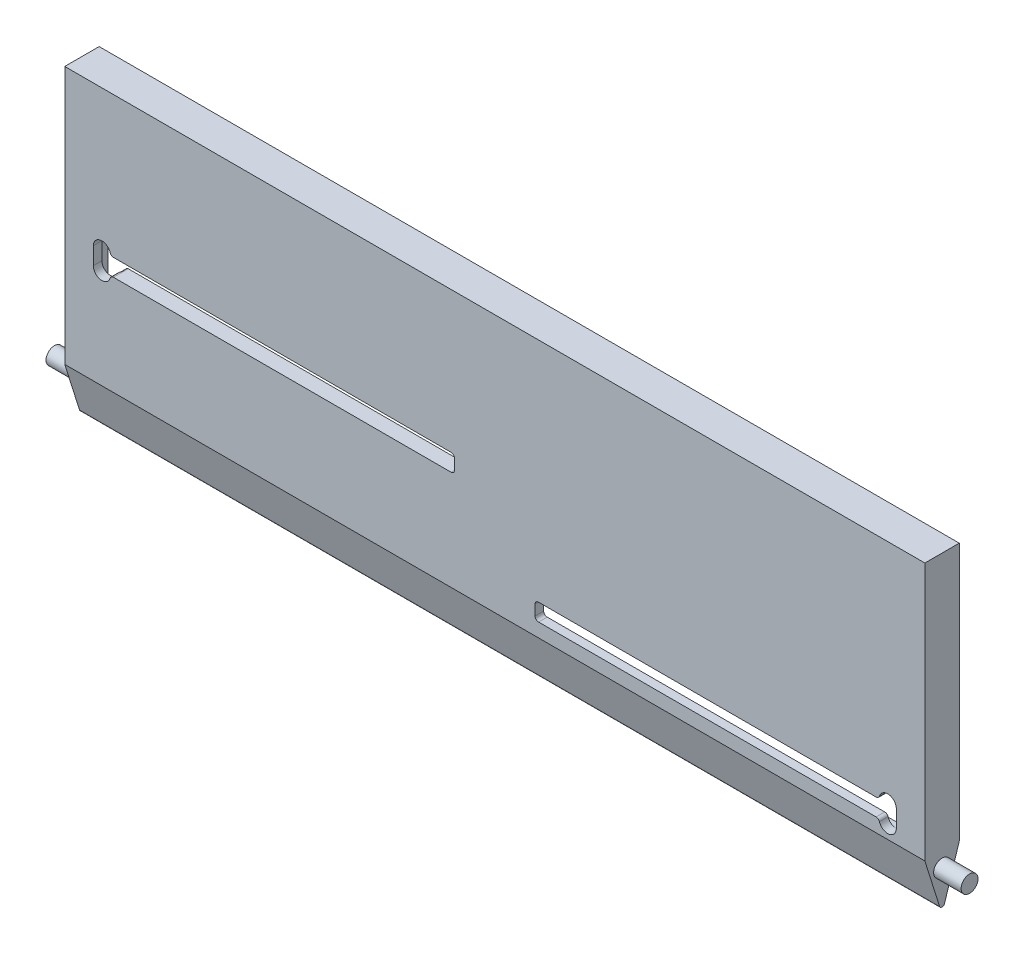
SolidWorks part; units mm, degrees
material "ABS"
ref_plane "Face" through (0, 0, 0) normal (0, 0, 1) x (1, 0, 0)
ref_plane "Dessus" through (0, 0, 0) normal (0, 1, 0) x (1, 0, 0)
ref_plane "Droite" through (0, 0, 0) normal (1, 0, 0) x (0, 0, -1)
sketch "Esquisse1" plane through (0, 0, 0) normal (1, 0, 0) x (0, 0, -1)
  line L0 (5, 15.858) -> (0, 0)
  line L1 (-5, 15.858) -> (5, 15.858) construction
  line L2 (-5, 15.858) -> (-5, 90.858)
  line L3 (-5, 90.858) -> (5, 90.858)
  line L4 (5, 15.858) -> (5, 90.858)
  line L5 (0, 0) -> (-5, 15.858)
  line L6 (0, 15.858) -> (0, 0) construction
  dimension "D1" = 10
  dimension "D2" = 75
  dimension "D3" = 35
extrude "Boss.-Extru.1" add sketch "Esquisse1" along normal blind 125
sketch "Esquisse2" plane through (125, 0, 0) normal (-1, 0, 0) x (0, 0, 1)
  line L2 (-2.3843, 10.8875) -> (0, 3.3255) construction
  line L3 (0, 3.3255) -> (2.3843, 10.8875) construction
  line L4 (5, 15.858) -> (0, 0) construction
  line L5 (0, 0) -> (-5, 15.858) construction
  circle A0 centre (0, 11.6393) radius 2.5 construction
  circle A1 centre (0, 11.6393) radius 2.45
  dimension "D1" = 5
  dimension "D4" = 4.9
  dimension "D2" = 1
  dimension "D3" = 1
extrude "Boss.-Extru.2" add sketch "Esquisse2" against normal blind 8
mirror "Symétrie1" about plane through (0, 0, 0) normal (1, 0, 0) of "Boss.-Extru.1", "Boss.-Extru.2"
fillet "Congé1" radius 0.75 1 edges at (0, 0, 0)
shell "Coque1" thickness 2.5 removed face at (0, 9.0633, -2.8576) removed face at (0, 53.358, -5)
sketch "Esquisse3" plane through (0, 0, 5) normal (0, 0, 1) x (1, 0, 0)
  line L0 (114.2, 19.858) -> (114.2, 24.858) construction
  line L2 (116.7, 19.858) -> (116.7, 24.858)
  line L3 (114.2, 22.358) -> (116.7, 22.358) construction
  line L4 (110.8459, 24.858) -> (12.7, 24.858)
  line L6 (110.8459, 19.858) -> (12.7, 19.858)
  line L7 (11.7, 23.858) -> (11.7, 20.858)
  line L8 (125, 90.858) -> (125, 15.858) construction
  line L9 (125, 15.858) -> (-125, 15.858) construction
  arc A0 (111.8042, 19.1437) -> (116.7, 19.858) centre (114.2, 19.858) ccw
  arc A1 (116.7, 24.858) -> (111.8042, 25.5723) centre (114.2, 24.858) ccw
  arc A2 (12.7, 24.858) -> (11.7, 23.858) centre (12.7, 23.858) ccw
  arc A3 (12.7, 19.858) -> (11.7, 20.858) centre (12.7, 20.858) cw
  arc A4 (110.8459, 24.858) -> (111.8042, 25.5723) centre (110.8459, 25.858) ccw
  arc A5 (110.8459, 19.858) -> (111.8042, 19.1437) centre (110.8459, 18.858) cw
  point P11 (114.2, 22.358)
  point P34 (11.7, 24.858)
  point P39 (111.7, 24.858)
  dimension "D1" = 10
  dimension "D6" = 1
  dimension "D7" = 1
  dimension "D2" = 8.3
  dimension "D3" = 5
  dimension "D4" = 100
  dimension "D5" = 4
extrude "Enlèv. mat.-Extru.1" cut sketch "Esquisse3" against normal through all
sketch "Esquisse4" plane through (0, 0, 2.5) normal (0, 0, -1) x (-1, 0, 0)
  line L0 (0, 34.858) -> (0, 0) construction
  line L1 (-12.7, 24.858) -> (-110.8459, 24.858) construction
  circle A0 centre (0, 34.858) radius 3.25
  circle A1 centre (0, 34.858) radius 1.65
  dimension "D1" = 6.5
  dimension "D3" = 3.3
  dimension "D2" = 10
extrude "Boss.-Extru.3" add sketch "Esquisse4" along normal blind 6
ref_axis "Axe1" through (0, 34.858, -3.5) along (0, 0, 1)
pattern_circular "Répétition circulaire1" count 2 over 360 about axis through (0, 34.858, -3.5) along (0, 0, 1) of "Enlèv. mat.-Extru.1"
sketch "Esquisse5" plane through (0, 0, 2.5) normal (0, 0, -1) x (-1, 0, 0)
  line L0 (-13.25, 39.858) -> (-13.25, 29.858) construction
  line L1 (13.25, 39.858) -> (13.25, 29.858) construction
  line L2 (-13.25, 34.858) -> (13.25, 34.858) construction
  line L10 (-12.7, 25.558) -> (-110.8459, 25.558)
  line L11 (-12.7, 25.558) -> (-110.8459, 25.558) construction
  line L12 (-12.7, 25.558) -> (122.5, 25.558) construction
  line L13 (12.7, 44.158) -> (110.8459, 44.158)
  line L14 (12.7, 44.158) -> (110.8459, 44.158) construction
  line L15 (122.5, 15.858) -> (122.5, 88.358) construction
  line L16 (12.7, 44.158) -> (-122.5, 44.158) construction
  line L17 (-122.5, 88.358) -> (-122.5, 16.2428) construction
  line L18 (-122.5, 16.558) -> (122.5, 16.558) construction
  line L20 (122.5, 88.358) -> (122.5, 16.2428) construction
  line L21 (-122.5, 53.158) -> (122.5, 53.158) construction
  line L22 (-13.95, 39.858) -> (-13.95, 29.858)
  line L23 (12.55, 39.858) -> (12.55, 29.858)
  line L24 (-12.7, 26.258) -> (122.5, 26.258)
  line L25 (-12.7, 26.258) -> (-110.8459, 26.258)
  line L26 (-122.5, 15.858) -> (122.5, 15.858)
  line L27 (12.7, 43.458) -> (-122.5, 43.458)
  line L28 (12.7, 43.458) -> (110.8459, 43.458)
  line L29 (-122.5, 52.458) -> (122.5, 52.458)
  line L30 (-12.55, 39.858) -> (-12.55, 29.858)
  line L31 (13.95, 39.858) -> (13.95, 29.858)
  line L32 (-12.7, 24.858) -> (122.5, 24.858)
  line L33 (-12.7, 24.858) -> (-110.8459, 24.858)
  line L34 (-122.5, 17.258) -> (122.5, 17.258)
  line L35 (12.7, 44.858) -> (-122.5, 44.858)
  line L36 (12.7, 44.858) -> (110.8459, 44.858)
  line L37 (-122.5, 53.858) -> (122.5, 53.858)
  arc A0 (-13.95, 39.858) -> (-12.55, 39.858) centre (-13.25, 39.858) cw
  arc A1 (-13.95, 29.858) -> (-12.55, 29.858) centre (-13.25, 29.858) ccw
  arc A2 (12.55, 39.858) -> (13.95, 39.858) centre (13.25, 39.858) cw
  arc A3 (12.55, 29.858) -> (13.95, 29.858) centre (13.25, 29.858) ccw
  arc A4 (122.5, 26.258) -> (122.5, 24.858) centre (122.5, 25.558) cw
  arc A5 (-110.8459, 26.258) -> (-110.8459, 24.858) centre (-110.8459, 25.558) ccw
  arc A6 (-122.5, 15.858) -> (-122.5, 17.258) centre (-122.5, 16.558) cw
  arc A7 (122.5, 15.858) -> (122.5, 17.258) centre (122.5, 16.558) ccw
  arc A8 (-122.5, 43.458) -> (-122.5, 44.858) centre (-122.5, 44.158) cw
  arc A9 (110.8459, 43.458) -> (110.8459, 44.858) centre (110.8459, 44.158) ccw
  arc A10 (-122.5, 52.458) -> (-122.5, 53.858) centre (-122.5, 53.158) cw
  arc A11 (122.5, 52.458) -> (122.5, 53.858) centre (122.5, 53.158) ccw
  point P4 (0, 34.858)
  dimension "D1" = 26.5
  dimension "D2" = 10
  dimension "D5" = 9
  dimension "D6" = 9
  dimension "D3" = 0.7
  dimension "D4" = 0.7
  dimension "D7" = 0.7
  dimension "D8" = 0.7
extrude "Boss.-Extru.4" add sketch "Esquisse5" along normal blind 1.8
